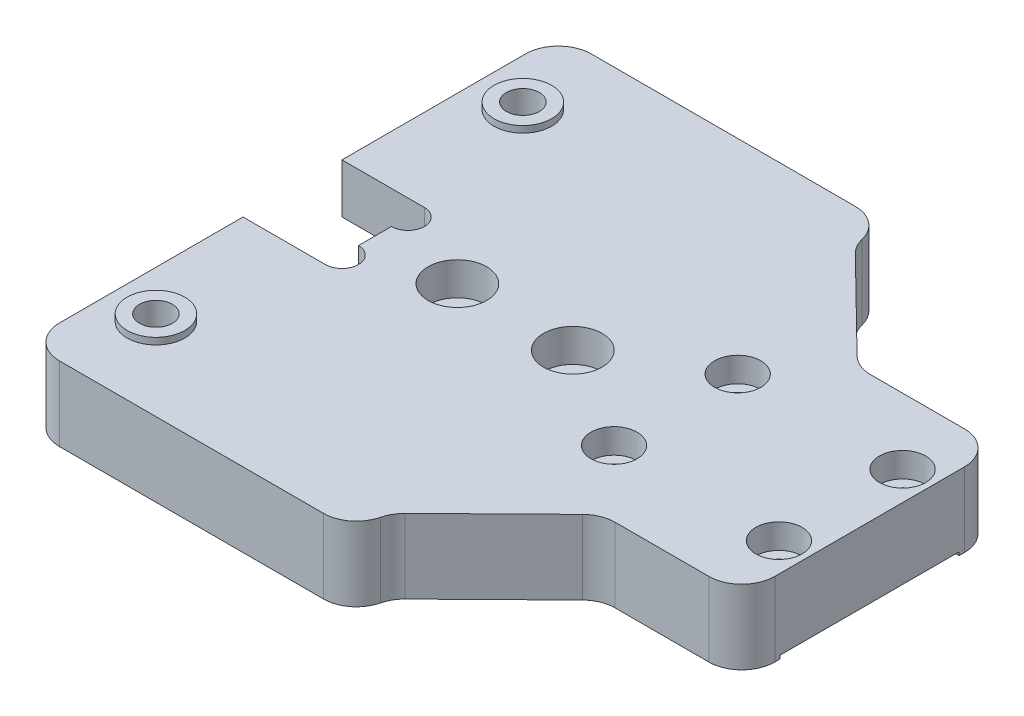
SolidWorks part; units mm, degrees
ref_plane "Front Plane" through (0, 0, 0) normal (0, 0, 1) x (1, 0, 0)
ref_plane "Top Plane" through (0, 0, 0) normal (0, 1, 0) x (1, 0, 0)
ref_plane "Right Plane" through (0, 0, 0) normal (1, 0, 0) x (0, 0, -1)
sketch "Sketch1" plane through (0, 0, 0) normal (0, 1, 0) x (1, 0, 0)
  line L0 (0, 0) -> (21.5, 0) construction
  line L5 (21.5, 20) -> (21.5, -20)
  line L6 (21.5, -20) -> (-20.5, -32.5)
  line L7 (-20.5, -32.5) -> (-84.5, -32.5)
  line L8 (-84.5, -32.5) -> (-84.5, 32.5)
  line L11 (-84.5, 32.5) -> (-20.5, 32.5)
  line L12 (-20.5, 32.5) -> (21.5, 20)
  circle A0 centre (0, 0) radius 12
  point P7 (21.5, 0)
  dimension "D4" = 24
  dimension "D6" = 9.5
  dimension "D1" = 40
  dimension "D2" = 106
  dimension "D3" = 65
  dimension "D5" = 64
extrude "Boss-Extrude1" add sketch "Sketch1" along normal mid plane 9
sketch "Sketch2" plane through (0, 4.5, 0) normal (0, 1, 0) x (1, 0, 0)
  line L0 (0, 0) -> (-19.5, 0) construction
  line L1 (-15.5, -15.5) -> (15.5, -15.5) construction
  line L2 (-15.5, -15.5) -> (-15.5, 15.5) construction
  line L3 (-15.5, 15.5) -> (15.5, 15.5) construction
  line L4 (15.5, -15.5) -> (15.5, 15.5) construction
  line L5 (-15.5, -15.5) -> (15.5, 15.5) construction
  line L6 (-15.5, 15.5) -> (15.5, -15.5) construction
  line L7 (-19.5, 27.5) -> (-19.5, -27.5) construction
  line L9 (-84.5, 32.5) -> (-84.5, -32.5) construction
  circle A0 centre (15.5, 15.5) radius 1.7
  circle A1 centre (-15.5, 15.5) radius 1.7
  circle A2 centre (-15.5, -15.5) radius 1.7
  circle A3 centre (15.5, -15.5) radius 1.7
  circle A4 centre (-19.5, 27.5) radius 1.7
  circle A5 centre (-19.5, -27.5) radius 1.7
  point P0 (0, 0)
  dimension "D2" = 3.4
  dimension "D1" = 31
  dimension "D3" = 55
  dimension "D4" = 65
extrude "Cut-Extrude1" cut sketch "Sketch2" against normal through all
fillet "Fillet1" radius 4 6 edges at (-84.5, 0, -32.5) (-84.5, 0, 32.5) (-20.5, 0, 32.5) (21.5, 0, 20) (-20.5, 0, -32.5) (21.5, 0, -20)
sketch "Sketch5" plane through (0, 4.5, 0) normal (0, 1, 0) x (1, 0, 0)
  line L0 (-24.5, 32.5) -> (-24.5, 10)
  line L1 (-21.0826, 32.5) -> (-80.5, 32.5) construction
  line L2 (-80.5, -32.5) -> (-21.0826, -32.5) construction
  line L3 (-84.5, 28.5) -> (-84.5, -28.5) construction
  line L4 (-24.5, 32.5) -> (26.912, 32.5)
  line L5 (-24.5, -10) -> (-29.5, -10) construction
  line L6 (-24.5, -10) -> (-24.5, 10) construction
  line L7 (-24.5, 10) -> (-29.5, 10) construction
  line L8 (-29.5, -10) -> (-29.5, 10) construction
  line L9 (26.912, 32.5) -> (26.912, -32.5)
  line L11 (-24.5, -32.5) -> (26.912, -32.5)
  line L12 (-24.5, 10) -> (-24.5, -10) construction
  line L13 (-24.5, -10) -> (-24.5, -32.5)
  line L14 (-29.5, 0) -> (0, 0) construction
  line L15 (-24.5, 10) -> (-24.5, -10)
  dimension "D1" = 60
  dimension "D2" = 20
  dimension "D3" = 5
extrude "Cut-Extrude4" cut sketch "Sketch5" against normal through all
fillet "Fillet3" radius 4 2 edges at (-24.5, 0, -32.5) (-24.5, 0, 32.5)
sketch "Sketch6" plane through (0, -4.5, 0) normal (0, -1, 0) x (1, 0, 0)
  line L0 (-48, -7.5) -> (-48, 7.5) construction
  line L3 (-48, -7.5) -> (-28, -7.5) construction
  line L4 (-28, -7.5) -> (-28, 7.5) construction
  line L5 (-28, 7.5) -> (-48, 7.5) construction
  line L6 (-24.5, -28.5) -> (-24.5, 28.5) construction
  line L7 (-28.5, -32.5) -> (-80.5, -32.5) construction
  circle A0 centre (-48, -7.5) radius 1.5
  circle A1 centre (-48, 7.5) radius 1.5
  circle A2 centre (-28, 7.5) radius 1.5
  circle A3 centre (-28, -7.5) radius 1.5
  dimension "D3" = 3.5
  dimension "D5" = 3
  dimension "D1" = 15
  dimension "D2" = 20
  dimension "D4" = 25
extrude "Cut-Extrude5" cut sketch "Sketch6" against normal blind 41
sketch "Sketch7" plane through (0, 4.5, 0) normal (0, 1, 0) x (1, 0, 0)
  line L0 (-84.5, 28.5) -> (-84.5, -28.5) construction
  line L1 (-84.5, 10) -> (-54.5, 10)
  line L2 (-84.5, 10) -> (-84.5, -10)
  line L3 (-84.5, -10) -> (-54.5, -10)
  line L4 (-54.5, 10) -> (-54.5, -10)
  line L5 (-28.5, 32.5) -> (-80.5, 32.5) construction
  dimension "D1" = 20
  dimension "D2" = 22.5
  dimension "D3" = 30
extrude "Cut-Extrude6" cut sketch "Sketch7" against normal blind 3 from offset 6 offset against normal yes
sketch "Sketch8" plane through (0, 4.5, 0) normal (0, 1, 0) x (1, 0, 0)
  line L0 (-84.5, 28.5) -> (-84.5, -28.5) construction
  line L1 (-84.5, 15.5) -> (-24.5, 15.5)
  line L2 (-84.5, 15.5) -> (-84.5, 32.5)
  line L3 (-84.5, 32.5) -> (-24.5, 32.5)
  line L4 (-24.5, 15.5) -> (-24.5, 32.5)
  line L5 (-84.5, 28.5) -> (-84.5, -28.5) construction
  line L7 (-24.5, 28.5) -> (-24.5, -28.5) construction
  line L8 (-28.5, 32.5) -> (-80.5, 32.5) construction
  line L9 (-84.5, 0) -> (-24.5, 0) construction
  line L11 (-84.5, -32.5) -> (-24.5, -32.5)
  line L12 (-24.5, -15.5) -> (-24.5, -32.5)
  line L13 (-84.5, -15.5) -> (-24.5, -15.5)
  line L14 (-84.5, -15.5) -> (-84.5, -32.5)
  dimension "D1" = 17
extrude "Cut-Extrude8" cut sketch "Sketch8" against normal blind 9
fillet "Fillet6" radius 4 2 edges at (-24.5, 0, -15.5) (-24.5, 0, 15.5)
sketch "Sketch9" plane through (0, 4.5, 0) normal (0, 1, 0) x (1, 0, 0)
  line L0 (-84.5, 15.5) -> (-28.5, 15.5) construction
  line L1 (-54.5, 10) -> (-94.5, 10)
  line L2 (-54.5, 10) -> (-54.5, 32.25)
  line L3 (-54.5, 32.25) -> (-94.5, 32.25)
  line L4 (-94.5, 10) -> (-94.5, 32.25)
  line L5 (-24.5, 11.5) -> (-24.5, -11.5) construction
  line L7 (-24.5, 0) -> (-84.5, 0) construction
  line L9 (-54.5, -32.25) -> (-94.5, -32.25)
  line L10 (-94.5, -10) -> (-94.5, -32.25)
  line L11 (-54.5, -10) -> (-94.5, -10)
  line L12 (-54.5, -10) -> (-54.5, -32.25)
  line L13 (-84.5, 15.5) -> (-84.5, -15.5) construction
  dimension "D1" = 30
  dimension "D2" = 40
  dimension "D3" = 22.25
  dimension "D4" = 5.5
extrude "Boss-Extrude3" add sketch "Sketch9" against normal blind 9
fillet "Fillet7" radius 4 4 edges at (-94.5, 0, -32.25) (-54.5, 0, -32.25) (-54.5, 0, 32.25) (-94.5, 0, 32.25)
sketch "Sketch13" plane through (0, 4.5, 0) normal (0, 1, 0) x (1, 0, 0)
  line L0 (-84.5, 0) -> (-24.5, 0) construction
  line L1 (-84.5, 10) -> (-84.5, -10) construction
  line L2 (-24.5, 11.5) -> (-24.5, -11.5) construction
  line L3 (-58.5, 32.25) -> (-90.5, 32.25) construction
  line L4 (-94.5, 28.25) -> (-94.5, 10) construction
  circle A0 centre (-88.81, 22.25) radius 3.5
  circle A1 centre (-88.81, -22.25) radius 3.5
  dimension "D1" = 7
  dimension "D2" = 10
  dimension "D3" = 5.69
extrude "Boss-Extrude5" add sketch "Sketch13" along normal blind 0.8
sketch "Sketch10" plane through (0, 4.5, 0) normal (0, 1, 0) x (1, 0, 0)
  line L0 (-94.5, -10) -> (-94.5, -28.25) construction
  line L1 (-90.5, -32.25) -> (-58.5, -32.25) construction
  line L2 (-24.5, 0) -> (-84.5, 0) construction
  line L3 (-24.5, 11.5) -> (-24.5, -11.5) construction
  line L4 (-84.5, 10) -> (-84.5, -10) construction
  circle A0 centre (-88.81, -22.25) radius 2
  circle A1 centre (-88.81, 22.25) radius 2
  dimension "D2" = 10
  dimension "D3" = 4
  dimension "D1" = 5.69
extrude "Cut-Extrude9" cut sketch "Sketch10" against normal blind 9 and the other way blind 2
sketch "Sketch11" plane through (0, 4.5, 0) normal (0, 1, 0) x (1, 0, 0)
  line L0 (-54.5, 28.25) -> (-41.5, 15.5)
  line L1 (-54.5, 15.5) -> (-54.5, 28.25) construction
  line L2 (-54.5, 15.5) -> (-28.5, 15.5) construction
  line L3 (-54.5, -28.25) -> (-41.5, -15.5)
  line L4 (-28.5, -15.5) -> (-54.5, -15.5) construction
  line L5 (-54.5, -28.25) -> (-54.5, -15.5) construction
  line L6 (-54.5, 28.25) -> (-54.5, 15.5)
  line L7 (-54.5, 15.5) -> (-41.5, 15.5)
  line L8 (-54.5, -28.25) -> (-54.5, -15.5)
  line L9 (-54.5, -15.5) -> (-41.5, -15.5)
  arc A0 (-58.5, -32.25) -> (-54.5, -28.25) centre (-58.5, -28.25) ccw construction
  arc A1 (-54.5, 28.25) -> (-58.5, 32.25) centre (-58.5, 28.25) ccw construction
extrude "Boss-Extrude4" add sketch "Sketch11" against normal blind 9
sketch "Sketch14" plane through (0, -1.5, 0) normal (0, -1, 0) x (1, 0, 0)
  line L0 (-84.5, 0) -> (-24.5, 0) construction
  line L1 (-84.5, -10) -> (-84.5, 10) construction
  line L2 (-24.5, -11.5) -> (-24.5, 11.5) construction
  line L3 (-54.5, 10) -> (-54.5, -10) construction
  circle A0 centre (-74.5, 0) radius 2
  circle A1 centre (-60.5, 0) radius 2
  dimension "D1" = 4
  dimension "D2" = 4
  dimension "D3" = 6
  dimension "D4" = 14
extrude "Cut-Extrude10" cut sketch "Sketch14" against normal blind 16
sketch "Sketch15" plane through (0, -4.5, 0) normal (0, -1, 0) x (1, 0, 0)
  line L0 (-24.5, -11.5) -> (-24.5, 11.5) construction
  line L1 (-24.5, 10.85) -> (-32, 10.85)
  line L2 (-24.5, 10.85) -> (-24.5, -10.85)
  line L3 (-24.5, -10.85) -> (-32, -10.85)
  line L4 (-32, 10.85) -> (-32, -10.85)
  line L5 (-28.5, 15.5) -> (-41.5, 15.5) construction
  line L6 (-38, 15.5) -> (-38, -15.5) construction
  line L7 (-41.5, -15.5) -> (-28.5, -15.5) construction
  line L8 (-51.5, 10.85) -> (-44, 10.85)
  line L9 (-51.5, 10.85) -> (-51.5, -10.85)
  line L10 (-44, 10.85) -> (-44, -10.85)
  line L11 (-51.5, -10.85) -> (-44, -10.85)
  dimension "D1" = 7.5
  dimension "D2" = 21.7
  dimension "D3" = 4.65
  dimension "D4" = 13.5
extrude "Cut-Extrude11" cut sketch "Sketch15" against normal blind 0.4
chamfer "Chamfer2" distance 0.4 angle 45 2 edges at (-32, -4.1, 0) (-44, -4.1, 0)
chamfer "Chamfer3" distance 0.6 angle 45 1 edges at (-51.5, -4.1, 0)
sketch "Sketch16" plane through (-84.5, 0, 0) normal (-1, 0, 0) x (0, 0, 1)
  line L0 (-10, 4.5) -> (10, 4.5) construction
  line L1 (-10, 4.5) -> (-6, 4.5)
  line L2 (-10, 4.5) -> (-10, -1.5)
  line L3 (-10, -1.5) -> (-6, -1.5)
  line L4 (-6, 4.5) -> (-6, -1.5)
  line L5 (-10, 4.5) -> (-10, -1.5) construction
  line L6 (-10, -1.5) -> (10, -1.5) construction
  line L8 (10, 4.5) -> (6, 4.5)
  line L9 (10, 4.5) -> (10, -1.5)
  line L10 (10, -1.5) -> (6, -1.5)
  line L11 (6, 4.5) -> (6, -1.5)
  line L12 (10, -1.5) -> (10, 4.5) construction
  dimension "D1" = 4
extrude "Boss-Extrude6" add sketch "Sketch16" along normal blind 10
sketch "Sketch17" plane through (0, 4.5, 0) normal (0, 1, 0) x (1, 0, 0)
  line L0 (-84.5, 0) -> (-24.5, 0) construction
  line L1 (-84.5, 6) -> (-84.5, -6) construction
  line L2 (-24.5, 11.5) -> (-24.5, -11.5) construction
  line L3 (-94.5, 6) -> (-84.5, 6) construction
  circle A0 centre (-84.5, 4) radius 2
  circle A1 centre (-84.5, -4) radius 2
  dimension "D1" = 4
extrude "Cut-Extrude12" cut sketch "Sketch17" against normal blind 12.4
sketch "Sketch18" plane through (0, 4.5, 0) normal (0, 1, 0) x (1, 0, 0)
  line L0 (-60.5, 0) -> (-74.5, 0) construction
  line L1 (-90.5, -32.25) -> (-58.5, -32.25) construction
  line L2 (-84.5, 2) -> (-84.5, -2) construction
  circle A0 centre (-74.5, 0) radius 3.55
  circle A1 centre (-60.5, 0) radius 3.55
  dimension "D1" = 7.1
  dimension "D2" = 14
  dimension "D3" = 32.25
  dimension "D4" = 10
extrude "Cut-Extrude13" cut sketch "Sketch18" against normal blind 4
sketch "Sketch19" plane through (0, 4.5, 0) normal (0, 1, 0) x (1, 0, 0)
  line L0 (-48, 7.5) -> (-48, -7.5) construction
  line L1 (-48, -7.5) -> (-28, -7.5) construction
  line L2 (-28, -7.5) -> (-28, 7.5) construction
  line L3 (-28, 7.5) -> (-48, 7.5) construction
  line L4 (-41.5, 15.5) -> (-28.5, 15.5) construction
  line L5 (-24.5, 11.5) -> (-24.5, -11.5) construction
  circle A0 centre (-48, 7.5) radius 2.8
  circle A1 centre (-28, 7.5) radius 2.8
  circle A2 centre (-48, -7.5) radius 2.8
  circle A3 centre (-28, -7.5) radius 2.8
  dimension "D3" = 5.6
  dimension "D1" = 15
  dimension "D2" = 20
  dimension "D4" = 8
  dimension "D5" = 3.5
extrude "Cut-Extrude14" cut sketch "Sketch19" against normal blind 3
sketch "Sketch20" plane through (0, -4.5, 0) normal (0, -1, 0) x (1, 0, 0)
  line L0 (-32, 10.85) -> (-32, -10.85) construction
  line L1 (-24.5, 10.85) -> (-32, 10.85) construction
  line L2 (-31.6, -10.85) -> (-24.5, -10.85) construction
  line L3 (-51.3, -10.85) -> (-51.3, 10.85) construction
  line L4 (-44, -10.85) -> (-44, 10.85) construction
  line L5 (-44, 10.85) -> (-51.3, 10.85) construction
  line L6 (-51.3, -10.85) -> (-44, -10.85) construction
  circle A0 centre (-32, 8.85) radius 2
  circle A1 centre (-32, -8.85) radius 2
  circle A2 centre (-51.3, 8.85) radius 2
  circle A3 centre (-51.3, -8.85) radius 2
  circle A4 centre (-44, -8.85) radius 2
  circle A5 centre (-44, 8.85) radius 2
  dimension "D1" = 4
extrude "Cut-Extrude15" cut sketch "Sketch20" against normal blind 0.4
fillet "Fillet8" radius 4 4 edges at (-54.5, 0, -28.25) (-41.5, 0, -15.5) (-41.5, 0, 15.5) (-54.5, 0, 28.25)
sketch "Sketch21" plane through (0, -4.5, 0) normal (0, -1, 0) x (1, 0, 0)
  line L0 (-94.5, 10) -> (-54.5, 10) construction
  line L1 (-54.5, 10) -> (-54.5, -10) construction
  line L2 (-54.5, -10) -> (-94.5, -10) construction
  line L3 (-54.5, 10) -> (-54.5, -10) construction
  circle A0 centre (-56.5, 10) radius 2
  circle A1 centre (-56.5, -10) radius 2
  dimension "D1" = 4
extrude "Cut-Extrude16" cut sketch "Sketch21" against normal blind 3
